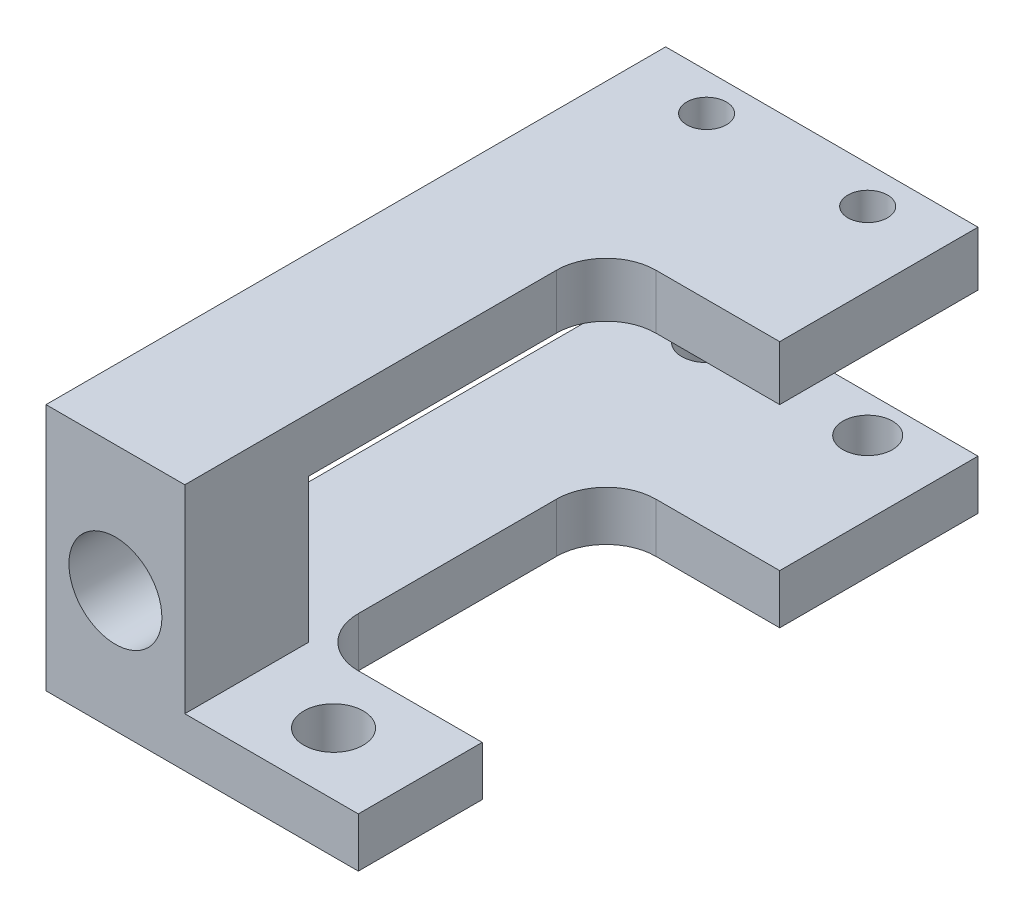
SolidWorks part; units mm, degrees
ref_plane "Front Plane" through (0, 0, 0) normal (0, 0, 1) x (1, 0, 0)
ref_plane "Top Plane" through (0, 0, 0) normal (0, 1, 0) x (1, 0, 0)
ref_plane "Right Plane" through (0, 0, 0) normal (1, 0, 0) x (0, 0, -1)
sketch "Sketch1" plane through (0, 0, 0) normal (0, 1, 0) x (1, 0, 0)
  line L1 (-6.3, -12.5) -> (6.3, -12.5)
  line L2 (-6.3, -12.5) -> (-6.3, 12.5)
  line L3 (-6.3, 12.5) -> (6.3, 12.5)
  line L4 (6.3, -12.5) -> (6.3, 12.5)
  line L5 (-6.3, -12.5) -> (6.3, 12.5) construction
  line L6 (-6.3, 12.5) -> (6.3, -12.5) construction
  point P0 (0, 0)
  dimension "D1" = 25
  dimension "D2" = 12.6
extrude "Boss-Extrude1" add sketch "Sketch1" along normal blind 10
sketch "Sketch2" plane through (0, 0, 12.5) normal (0, 0, 1) x (1, 0, 0)
  line L0 (-6.3, 10) -> (-6.3, 0) construction
  line L1 (-6.3, 7.8) -> (0.7, 7.8)
  line L2 (-6.3, 7.8) -> (-6.3, 2)
  line L3 (-6.3, 2) -> (0.7, 2)
  line L4 (0.7, 7.8) -> (0.7, 2)
  line L5 (-6.3, 0) -> (6.3, 0) construction
  dimension "D1" = 5.8
  dimension "D2" = 7
  dimension "D3" = 2
extrude "Cut-Extrude1" [suppressed] cut sketch "Sketch2" against normal through all
sketch "Sketch3" [suppressed] plane through (0.7, 0, 0) normal (-1, 0, 0) x (0, 0, 1)
  line L1 (-12.5, 2) -> (7.5, 2)
  line L2 (-12.5, 2) -> (-12.5, 7.8)
  line L3 (-12.5, 7.8) -> (7.5, 7.8)
  line L4 (7.5, 2) -> (7.5, 7.8)
  dimension "D1" = 20
  dimension "D2" = 5.8
extrude "Cut-Extrude2" [suppressed] cut sketch "Sketch3" against normal through all
sketch "Sketch4" [suppressed] plane through (0, 0, 7.5) normal (0, 0, -1) x (-1, 0, 0)
  line L0 (-0.7, 7.8) -> (-6.3, 2) construction
  line L1 (-6.3, 7.8) -> (-0.7, 2) construction
  circle A0 centre (-3.5, 4.9) radius 1.875
  point P8 (-3.5, 4.9)
  dimension "D1" = 3.75
sketch "Sketch6" [suppressed] plane through (0, 2, 0) normal (0, 1, 0) x (1, 0, 0)
  circle A0 centre (3.15, 11) radius 1 construction
  circle A1 centre (3.15, 11) radius 1
  circle A2 centre (-3.35, 11) radius 1
  dimension "D1" = 2
extrude "Cut-Extrude5" [suppressed] cut sketch "Sketch6" against normal through all
sketch "Sketch7" [suppressed] plane through (0, 10, 0) normal (0, 1, 0) x (1, 0, 0)
  circle A0 centre (3.15, 11) radius 1 construction
  circle A1 centre (3.15, 11) radius 1
  circle A2 centre (-3.35, 11) radius 1 construction
  circle A3 centre (-3.35, 11) radius 1
hole_wizard "Tap Drill for M2x0.4 Tap1" [suppressed] positions "3DSketch1" profile "Sketch8" hole size "M2x0.4" standard "ANSI Metric"
sketch3d "3DSketch1" [suppressed]
  point P0 (3.15, 10, -11)
  point P4 (-3.35, 10, -11)
sketch "Sketch8" plane through (3.15, 10, -11) normal (1, 0, 0) x (0, 0, 1)
  line L0 (0, 0) -> (0, 10)
  line L1 (0, 10) -> (0.8, 10)
  line L2 (0.8, 10) -> (0.8, 0)
  line L5 (0.8, 0) -> (0, 0)
  line L11 (0, -6.35) -> (0, 107.95) construction
  dimension "Thru Hole Dia." = 1.6
  dimension "Thru Hole Depth" = 10
sketch "Sketch9" [suppressed] plane through (0, 2, 0) normal (0, 1, 0) x (1, 0, 0)
  line L0 (0.7, -7.5) -> (0.7, -12.5) construction
  line L1 (0.7, -7.5) -> (-6.3, -7.5)
  line L2 (0.7, -7.5) -> (0.7, 4.5)
  line L3 (0.7, 4.5) -> (-6.3, 4.5)
  line L4 (-6.3, -7.5) -> (-6.3, 4.5)
  line L5 (-6.3, 12.5) -> (-6.3, -12.5) construction
  line L6 (-6.3, -12.5) -> (0.7, -12.5) construction
  dimension "D1" = 12
  dimension "D2" = 5
extrude "Cut-Extrude6" [suppressed] cut sketch "Sketch9" against normal through all both and the other way through all
sketch "Sketch10" [suppressed] plane through (0, 10, 0) normal (0, 1, 0) x (1, 0, 0)
  line L1 (0.7, -7.5) -> (-6.3, -7.5)
  line L2 (0.7, -7.5) -> (0.7, -12.5)
  line L3 (0.7, -12.5) -> (-6.3, -12.5)
  line L4 (-6.3, -7.5) -> (-6.3, -12.5)
extrude "Cut-Extrude8" [suppressed] cut sketch "Sketch10" against normal up to surface (2.2 mm away)
fillet "Fillet1" [suppressed] radius 2
extrude "Cut-Extrude7" [suppressed] cut sketch "Sketch4" against normal through all
sketch "Sketch11" [suppressed] plane through (0, 2, 0) normal (0, 1, 0) x (1, 0, 0)
  line L0 (0.7, -12.5) -> (-6.3, -7.5) construction
  line L1 (-6.3, -12.5) -> (0.7, -7.5) construction
  point P8 (-2.8, -10)
hole_wizard "M2 Clearance Hole1" [suppressed] positions "3DSketch3" profile "Sketch13" hole size "M2" standard "ANSI Metric"
sketch3d "3DSketch3" [suppressed]
  point P0 (-2.8, 2, 10)
sketch "Sketch13" plane through (-2.8, 2, 10) normal (1, 0, 0) x (0, 0, 1)
  line L0 (0, 0) -> (0, 2)
  line L1 (0, 2) -> (1.2, 2)
  line L2 (1.2, 2) -> (1.2, 0)
  line L5 (1.2, 0) -> (0, 0)
  line L11 (0, -6.35) -> (0, 107.95) construction
  dimension "Thru Hole Dia." = 2.4
  dimension "Thru Hole Depth" = 2
sketch "Sketch14" plane through (0, 0, 12.5) normal (0, 0, 1) x (1, 0, 0)
  line L0 (6.3, 10) -> (6.3, 0) construction
  line L1 (6.3, 7.8) -> (-0.7, 7.8)
  line L2 (6.3, 7.8) -> (6.3, 2)
  line L3 (6.3, 2) -> (-0.7, 2)
  line L4 (-0.7, 7.8) -> (-0.7, 2)
  line L5 (-6.3, 0) -> (6.3, 0) construction
  dimension "D1" = 7
  dimension "D2" = 5.8
  dimension "D3" = 2
extrude "Cut-Extrude9" cut sketch "Sketch14" against normal through all
sketch "Sketch15" plane through (-0.7, 0, 0) normal (1, 0, 0) x (0, 0, -1)
  line L0 (12.5, 2) -> (-12.5, 2) construction
  line L1 (12.5, 7.8) -> (-7.5, 7.8)
  line L2 (12.5, 7.8) -> (12.5, 2)
  line L3 (12.5, 2) -> (-7.5, 2)
  line L4 (-7.5, 7.8) -> (-7.5, 2)
  dimension "D1" = 20
extrude "Cut-Extrude10" cut sketch "Sketch15" against normal through all
sketch "Sketch17" plane through (0, 2, 0) normal (0, 1, 0) x (1, 0, 0)
  line L0 (6.3, 12.5) -> (6.3, -12.5) construction
  line L1 (-0.7, -7.5) -> (6.3, -7.5)
  line L2 (-0.7, -7.5) -> (-0.7, 4.5)
  line L3 (-0.7, 4.5) -> (6.3, 4.5)
  line L4 (6.3, -7.5) -> (6.3, 4.5)
  dimension "D1" = 12
extrude "Cut-Extrude11" cut sketch "Sketch17" against normal through all both and the other way through all
sketch "Sketch18" plane through (0, 0, 7.5) normal (0, 0, -1) x (-1, 0, 0)
  line L0 (0.7, 7.8) -> (6.3, 2) construction
  line L1 (6.3, 7.8) -> (0.7, 2) construction
  circle A0 centre (3.5, 4.9) radius 1.875
  dimension "D1" = 3.75
extrude "Cut-Extrude12" cut sketch "Sketch18" against normal through all
sketch "Sketch19" plane through (0, 10, 0) normal (0, 1, 0) x (1, 0, 0)
  line L1 (6.3, -12.5) -> (-0.7, -12.5)
  line L2 (6.3, -12.5) -> (6.3, -7.5)
  line L3 (6.3, -7.5) -> (-0.7, -7.5)
  line L4 (-0.7, -12.5) -> (-0.7, -7.5)
extrude "Cut-Extrude13" cut sketch "Sketch19" against normal up to surface (2.2 mm away) up to face at (-0.2333, 7.8, -3.1667)
fillet "Fillet2" radius 2 3 edges at (-0.7, 8.9, -4.5) (-0.7, 1, -4.5) (-0.7, 1, 7.5)
sketch "Sketch20" plane through (0, 0, 0) normal (0, -1, 0) x (1, 0, 0)
  circle A0 centre (3.35, -11) radius 1
  circle A1 centre (-3.15, -11) radius 1 construction
  circle A2 centre (-3.15, -11) radius 1
extrude "Cut-Extrude18" cut sketch "Sketch20" against normal blind 5
sketch "Sketch21" plane through (0, 10, 0) normal (0, 1, 0) x (1, 0, 0)
  circle A0 centre (3.35, 11) radius 1 construction
  circle A1 centre (3.35, 11) radius 1
  circle A2 centre (-3.15, 11) radius 1 construction
  circle A3 centre (-3.15, 11) radius 1
hole_wizard "Tap Drill for M2x0.4 Tap2" positions "3DSketch4" profile "Sketch22" hole size "M2x0.4" standard "ANSI Metric" end condition through all
sketch3d "3DSketch4"
  point P0 (3.35, 10, -11)
  point P3 (-3.15, 10, -11)
sketch "Sketch22" plane through (3.35, 10, -11) normal (1, 0, 0) x (0, 0, 1)
  line L0 (0, 0) -> (0, 10)
  line L1 (0, 10) -> (0.8, 10)
  line L2 (0.8, 10) -> (0.8, 0)
  line L5 (0.8, 0) -> (0, 0)
  line L11 (0, -6.35) -> (0, 107.95) construction
  dimension "Thru Hole Dia." = 1.6
  dimension "Thru Hole Depth" = 10
sketch "Sketch23" plane through (0, 2, 0) normal (0, 1, 0) x (1, 0, 0)
  line L0 (6.3, -12.5) -> (-0.7, -7.5) construction
  line L1 (-0.7, -12.5) -> (6.3, -7.5) construction
  point P8 (2.8, -10)
hole_wizard "M2 Clearance Hole2" positions "3DSketch5" profile "Sketch24" hole size "M2" standard "ANSI Metric" end condition through all
sketch3d "3DSketch5"
  point P0 (2.8, 2, 10)
sketch "Sketch24" plane through (2.8, 2, 10) normal (1, 0, 0) x (0, 0, 1)
  line L0 (0, 0) -> (0, 2)
  line L1 (0, 2) -> (1.2, 2)
  line L2 (1.2, 2) -> (1.2, 0)
  line L5 (1.2, 0) -> (0, 0)
  line L11 (0, -6.35) -> (0, 107.95) construction
  dimension "Thru Hole Dia." = 2.4
  dimension "Thru Hole Depth" = 2
